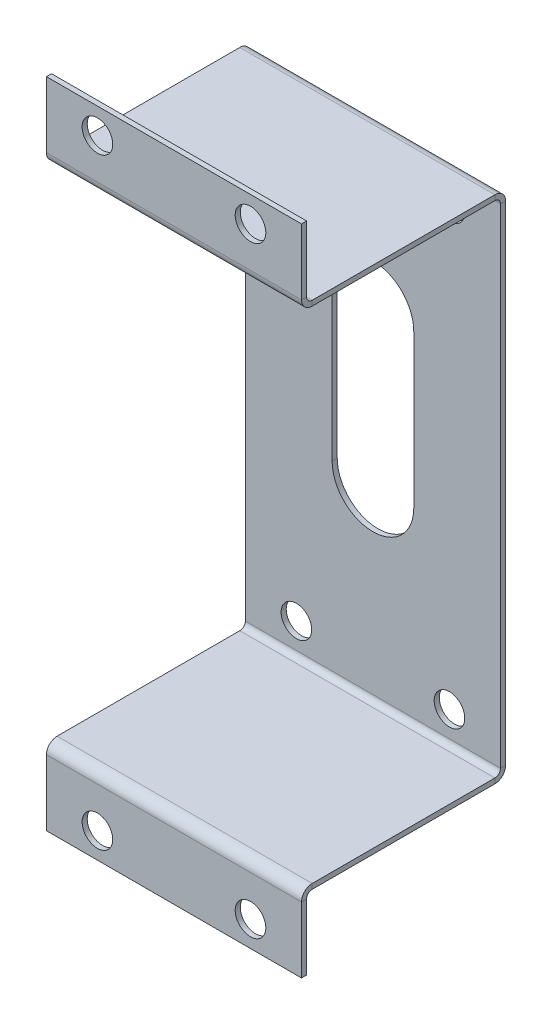
SolidWorks part; units mm, degrees
note: The reader was unsure of these and kept them because the rebuilt part matched: flange length of "Edge-Flange1", "Edge-Flange2".
ref_plane "Front Plane" through (0, 0, 0) normal (0, 0, 1) x (1, 0, 0)
ref_plane "Top Plane" through (0, 0, 0) normal (0, 1, 0) x (1, 0, 0)
ref_plane "Right Plane" through (0, 0, 0) normal (1, 0, 0) x (0, 0, -1)
sketch "Sketch3" plane through (0, 0, 0) normal (0, 0, 1) x (1, 0, 0)
  line L1 (25, 50) -> (-25, 50)
  line L2 (25, 50) -> (25, -50)
  line L3 (25, -50) -> (-25, -50)
  line L4 (-25, 50) -> (-25, -50)
  line L5 (25, 50) -> (-25, -50) construction
  line L6 (25, -50) -> (-25, 50) construction
  point P0 (0, 0)
  dimension "D1" = 100
  dimension "D2" = 50
base flange "Base-Flange1" sketch "Sketch3" thickness 1 reverse thickness direction no parameters "D1"=0.7366
edge flange "Edge-Flange1" sketch "Sketch12" flange profiles "Sketch12", "Sketch13" flange angle 90 flange length 40 flange position material inside bend radius 1.1 thickness 1 relief rectangular parameters "D6"=10, "D8"=1
sketch "Sketch12" plane through (0, -50, 0) normal (0, 1, 0) x (-1, 0, 0)
  line L2 (-25, 0) -> (-25, 39)
  line L3 (-25, 39) -> (25, 39)
  line L4 (25, 39) -> (25, 0)
  line L9 (25, 0) -> (-25, 0) construction
  line L10 (25, 0) -> (-25, 0)
sketch "Sketch13" plane through (0, 50, 0) normal (0, -1, 0) x (1, 0, 0)
  line L0 (25, 0) -> (-25, 0) construction
  line L1 (25, 0) -> (-25, 0)
  line L2 (25, 0) -> (25, 39)
  line L3 (25, 39) -> (-25, 39)
  line L4 (-25, 39) -> (-25, 0)
bend "EdgeBend1" bend radius 1.1 bend angle 90 parameters "D5"=1
bend "EdgeBend2" bend radius 1.1 bend angle 90 parameters "D5"=2
edge flange "Edge-Flange2" sketch "Sketch18" flange profiles "Sketch18", "Sketch19" flange angle 90 flange length 15 flange position material inside bend radius 1.1 thickness 1 relief rectangular parameters "D6"=10, "D8"=1
sketch "Sketch18" plane through (0, -50, 39) normal (0, 0, 1) x (-1, 0, 0)
  line L0 (25, 0) -> (-25, 0) construction
  line L1 (25, 0) -> (-25, 0)
  line L2 (-25, 0) -> (-25, 14)
  line L3 (-25, 14) -> (25, 14)
  line L4 (25, 14) -> (25, 0)
sketch "Sketch19" plane through (0, 50, 39) normal (0, 0, 1) x (1, 0, 0)
  line L0 (25, 0) -> (-25, 0) construction
  line L1 (25, 0) -> (-25, 0)
  line L2 (-25, 0) -> (-25, 14)
  line L3 (-25, 14) -> (25, 14)
  line L4 (25, 14) -> (25, 0)
bend "EdgeBend3" bend radius 1.1 bend angle 90 parameters "D5"=3
bend "EdgeBend4" bend radius 1.1 bend angle 90 parameters "D5"=4
sketch "Sketch20" plane through (0, 0, -1) normal (0, 0, -1) x (-1, 0, 0)
  line L0 (0, 47.9) -> (0, -47.9) construction
  line L1 (25, 47.9) -> (-25, 47.9) construction
  line L2 (-25, -47.9) -> (25, -47.9) construction
  line L3 (0, 17.7469) -> (0, -12.2531) construction
  line L4 (25, 47.9) -> (25, -47.9) construction
  line L5 (25, 0) -> (-25, 0) construction
  line L6 (-25, -47.9) -> (-25, 47.9) construction
  line L7 (8, 17.7469) -> (8, -12.2531)
  line L8 (-8, 17.7469) -> (-8, -12.2531)
  line L9 (-25, 64) -> (25, 64) construction
  arc A0 (8, 17.7469) -> (-8, 17.7469) centre (0, 17.7469) ccw
  arc A1 (-8, -12.2531) -> (8, -12.2531) centre (0, -12.2531) ccw
  circle A2 centre (15, 42.9) radius 3
  circle A3 centre (-15, 42.9) radius 3
  circle A4 centre (15, 59) radius 3
  circle A5 centre (-15, 59) radius 3
  circle A6 centre (-15, -59) radius 3
  circle A7 centre (15, -59) radius 3
  circle A8 centre (15, -42.9) radius 3
  circle A9 centre (-15, -42.9) radius 3
  point P14 (0, 2.7469)
  dimension "D2" = 8
  dimension "D3" = 6
  dimension "D6" = 5
  dimension "D7" = 5
  dimension "D1" = 30
  dimension "D4" = 10
  dimension "D5" = 10
extrude "Cut-Extrude1" cut sketch "Sketch20" against normal blind 94 normal cut yes
sketch "Bend-Lines1" [suppressed] plane through (0, 0, 0) normal (0, 1, 0) x (1, 0, 0)
sketch "Bounding-Box1" [suppressed] plane through (0, 0, 0) normal (0, 1, 0) x (1, 0, 0)
sheet metal parameters "Sheet-Metal2" thickness 1 parameters "D1"=0.7366
flat pattern "Flat-Pattern2" [suppressed]
sketch "Bend-Lines2" plane through (0, 0, 0) normal (0, 1, 0) x (1, 0, 0)
sketch3d "Bounding-Box2" [suppressed]
  line L0 (-25, 50, 0) -> (-25, -50, 0) construction
  line L1 (25, 50, 0) -> (25, -50, 0) construction
  line L2 (-25, 50, 0) -> (25, 50, 0) construction
  line L3 (-25, -50, 0) -> (25, -50, 0) construction
sheet metal parameters "Sheet-Metal3" thickness 1 parameters "D1"=0.7366
flat pattern "Flat-Pattern2"
sketch "Bend-Lines2" plane through (0, 0, 0) normal (0, 0, 1) x (1, 0, 0)
  line L0 (25, 49.0428) -> (-25, 49.0428) construction
  line L1 (-25, -49.0428) -> (25, -49.0428) construction
  line L2 (25, 49.0428) -> (-25, 49.0428) construction
  line L3 (-25, -49.0428) -> (25, -49.0428) construction
sketch3d "Bounding-Box2" [suppressed]
  line L0 (25, 88.0855, 0) -> (25, -88.0855, 0) construction
  line L1 (-25, 88.0855, 0) -> (-25, -88.0855, 0) construction
  line L2 (25, 88.0855, 0) -> (-25, 88.0855, 0) construction
  line L3 (25, -88.0855, 0) -> (-25, -88.0855, 0) construction
bend of the flat pattern "Flatten-<EdgeBend1>1"
bend of the flat pattern "Flatten-<EdgeBend2>1"
sheet metal parameters "Sheet-Metal4" thickness 1 parameters "D1"=0.7366
flat pattern "Flat-Pattern2"
sketch "Bend-Lines2" plane through (0, 0, 0) normal (0, 0, 1) x (1, 0, 0)
  line L0 (25, 49.0428) -> (-25, 49.0428) construction
  line L1 (-25, -49.0428) -> (25, -49.0428) construction
  line L2 (25, 49.0428) -> (-25, 49.0428) construction
  line L3 (-25, -49.0428) -> (25, -49.0428) construction
  line L4 (25, 87.1283) -> (-25, 87.1283) construction
  line L5 (-25, -87.1283) -> (25, -87.1283) construction
  line L6 (25, 87.1283) -> (-25, 87.1283) construction
  line L7 (-25, -87.1283) -> (25, -87.1283) construction
sketch3d "Bounding-Box2" [suppressed]
  line L0 (25, 101.171, 0) -> (25, -101.171, 0) construction
  line L1 (-25, 101.171, 0) -> (-25, -101.171, 0) construction
  line L2 (25, 101.171, 0) -> (-25, 101.171, 0) construction
  line L3 (25, -101.171, 0) -> (-25, -101.171, 0) construction
bend of the flat pattern "Flatten-<EdgeBend1>1"
bend of the flat pattern "Flatten-<EdgeBend2>1"
bend of the flat pattern "Flatten-<EdgeBend3>1"
bend of the flat pattern "Flatten-<EdgeBend4>1"
sheet metal parameters "Sheet-Metal5" thickness 1 parameters "D1"=0.7366
flat pattern "Flat-Pattern2"
sketch "Bend-Lines2" plane through (0, 0, 0) normal (0, 0, 1) x (1, 0, 0)
  line L0 (25, 49.0428) -> (-25, 49.0428) construction
  line L1 (-25, -49.0428) -> (25, -49.0428) construction
  line L2 (25, 49.0428) -> (-25, 49.0428) construction
  line L3 (-25, -49.0428) -> (25, -49.0428) construction
  line L4 (25, 87.1283) -> (-25, 87.1283) construction
  line L5 (-25, -87.1283) -> (25, -87.1283) construction
  line L6 (25, 87.1283) -> (-25, 87.1283) construction
  line L7 (-25, -87.1283) -> (25, -87.1283) construction
sketch3d "Bounding-Box2" [suppressed]
  line L0 (25, 101.171, 0) -> (25, -101.171, 0) construction
  line L1 (-25, 101.171, 0) -> (-25, -101.171, 0) construction
  line L2 (25, 101.171, 0) -> (-25, 101.171, 0) construction
  line L3 (25, -101.171, 0) -> (-25, -101.171, 0) construction
bend of the flat pattern "Flatten-<EdgeBend1>1"
bend of the flat pattern "Flatten-<EdgeBend2>1"
bend of the flat pattern "Flatten-<EdgeBend3>1"
bend of the flat pattern "Flatten-<EdgeBend4>1"
